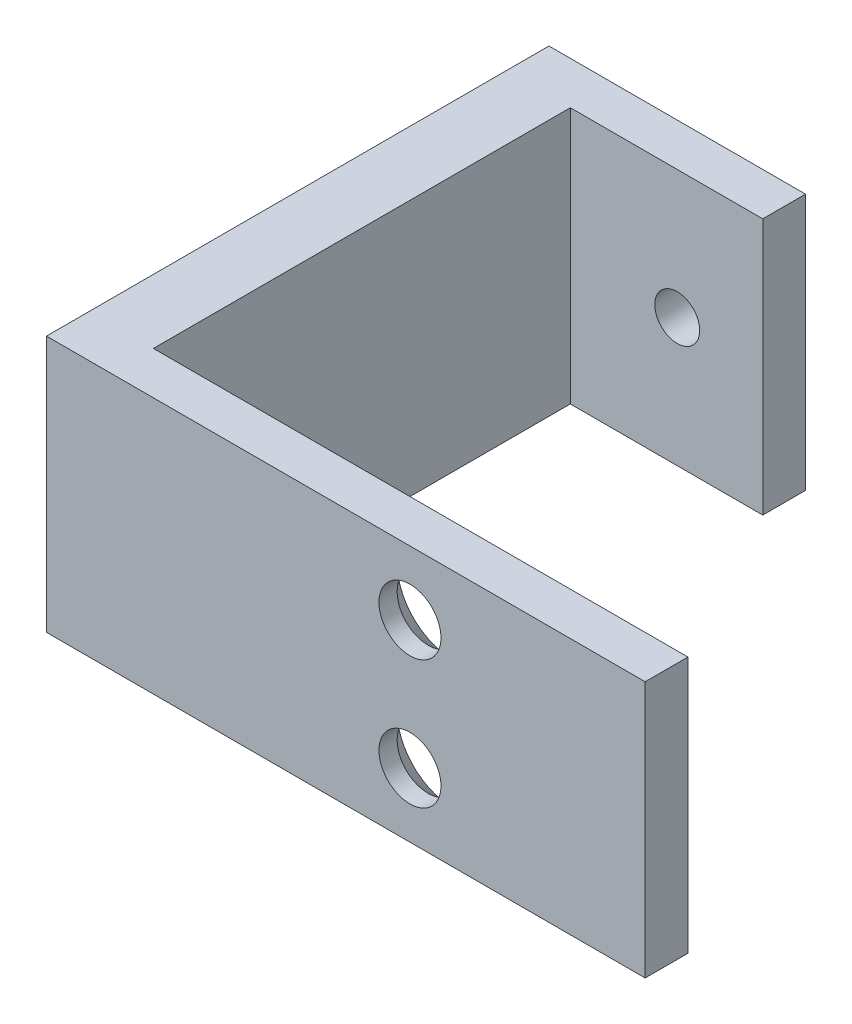
SolidWorks part; units mm, degrees
ref_plane "Front Plane" through (0, 0, 0) normal (0, 0, 1) x (1, 0, 0)
ref_plane "Top Plane" through (0, 0, 0) normal (0, 1, 0) x (1, 0, 0)
ref_plane "Right Plane" through (0, 0, 0) normal (1, 0, 0) x (0, 0, -1)
sketch "Sketch1" plane through (0, 0, 0) normal (0, 0, 1) x (1, 0, 0)
  line L1 (-44, -26) -> (-32, -26)
  line L2 (-44, -26) -> (-44, -14)
  line L3 (-44, -14) -> (-32, -14)
  line L4 (-32, -26) -> (-32, -14)
  circle A0 centre (-36, -20) radius 1.05
extrude "Link_Eye_Shelf" add sketch "Sketch1" along normal blind 2 from offset 23.5 offset against normal yes
sketch "Sketch2" plane through (0, 0, 0) normal (0, 0, 1) x (1, 0, 0)
  line L1 (-44, -26) -> (-41, -26)
  line L2 (-44, -26) -> (-44, -14)
  line L3 (-44, -14) -> (-41, -14)
  line L4 (-41, -26) -> (-41, -14)
extrude "Outboard_Web" add sketch "Sketch2" along normal blind 21.5 from offset 22.5 offset against normal yes
sketch "Sketch3" plane through (0, 0, 0) normal (0, 0, 1) x (1, 0, 0)
  line L1 (-44, -26) -> (-16, -26)
  line L2 (-44, -26) -> (-44, -14)
  line L3 (-44, -14) -> (-16, -14)
  line L4 (-16, -26) -> (-16, -14)
extrude "Carriage_Plate_Foot" add sketch "Sketch3" along normal blind 2 from offset 2 offset against normal yes
sketch "Sketch4" plane through (0, 0, -2) normal (0, 0, -1) x (-1, 0, 0)
  circle A0 centre (20, -23) radius 1.45
  circle A1 centre (20, -17) radius 1.45
sketch "Sketch5" plane through (0, 0, -2) normal (0, 0, -1) x (-1, 0, 0)
  circle A0 centre (20, -23) radius 2.6
  circle A1 centre (20, -17) radius 2.6
sketch "Sketch6" plane through (0, 0, -2) normal (0, 0, -1) x (-1, 0, 0)
  circle A0 centre (27, -23) radius 1.45
  circle A1 centre (27, -17) radius 1.45
extrude "YTab_D2p9" cut sketch "Sketch6" against normal blind 2.01
sketch "Sketch7" plane through (0, 0, -2) normal (0, 0, -1) x (-1, 0, 0)
  circle A0 centre (27, -23) radius 2.6
  circle A1 centre (27, -17) radius 2.6
extrude "YTab_CSK_D5p2" cut sketch "Sketch7" against normal blind 1.15 draft 45
